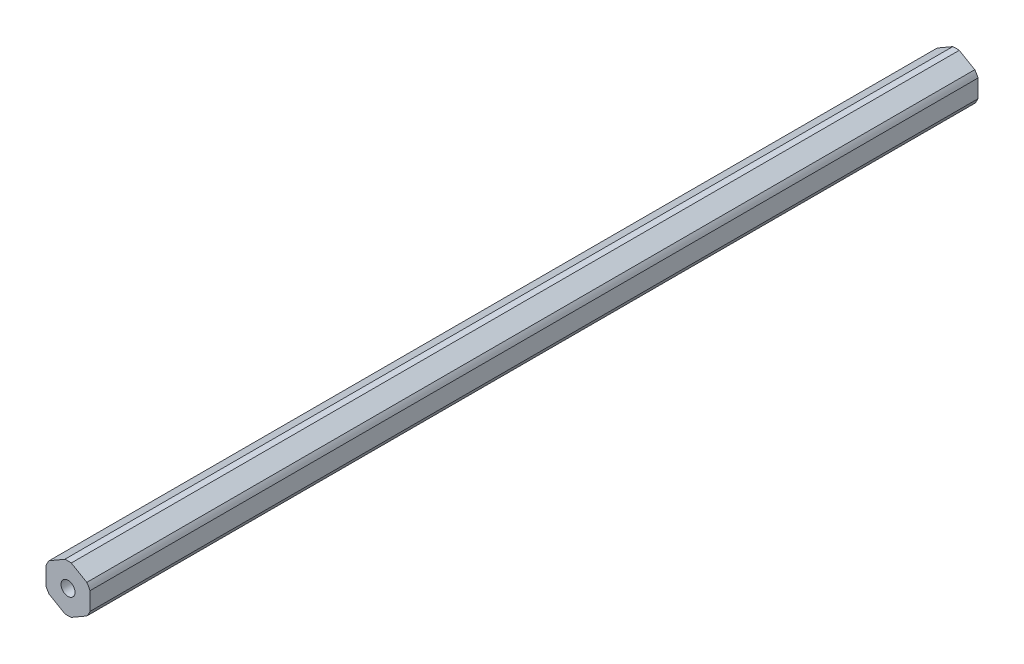
SolidWorks part; units mm, degrees
material "7075-T6 (SN)"
ref_plane "Front Plane" through (0, 0, 0) normal (0, 0, 1) x (1, 0, 0)
ref_plane "Top Plane" through (0, 0, 0) normal (0, 1, 0) x (1, 0, 0)
ref_plane "Right Plane" through (0, 0, 0) normal (1, 0, 0) x (0, 0, -1)
sketch "Sketch1" plane through (0, 0, 0) normal (0, 0, 1) x (1, 0, 0)
  line L1 (0, 7.3323) -> (-6.35, 3.6662)
  line L2 (-6.35, 3.6662) -> (-6.35, -3.6662)
  line L3 (-6.35, -3.6662) -> (0, -7.3323)
  line L4 (0, -7.3323) -> (6.35, -3.6662)
  line L5 (6.35, -3.6662) -> (6.35, 3.6662)
  line L6 (6.35, 3.6662) -> (0, 7.3323)
  circle A0 centre (0, 0) radius 6.35 construction
  circle A1 centre (0, 0) radius 6.858
  dimension "D1" = 12.7
  dimension "D2" = 13.716
extrude "Boss-Extrude1" add sketch "Sketch1" along normal mid plane 256.159 contours L5 A1 L6 L1 L2 L3 L4 region at (0, 0, 0)
sketch "Sketch2" plane through (0, 0, 128.0795) normal (0, 0, 1) x (1, 0, 0)
  circle A0 centre (0, 0) radius 2.0193
  dimension "D1" = 4.0386
extrude "Cut-Extrude1" [suppressed] cut sketch "Sketch2" against normal through all
hole_wizard "#10-32 Tapped Hole1" positions "3DSketch1" profile "Sketch3" tap size "#10-32" standard "ANSI Inch"
sketch3d "3DSketch1"
  line L0 (0, 0, 128.0795) -> (0, 0, -128.0795) construction
  point P0 (0, 0, 128.0795)
  point P4 (0, 0, -128.0795)
sketch "Sketch3" plane through (0, 0, 128.0795) normal (1, 0, 0) x (0, -1, 0)
  line L0 (0, 0) -> (0, 13.1513)
  line L1 (0, 13.1513) -> (2.0193, 11.938)
  line L2 (2.0193, 11.938) -> (2.0193, 0)
  line L5 (2.0193, 0) -> (0, 0)
  line L10 (0, 13.1513) -> (-2.0193, 11.938) construction
  line L11 (0, -6.35) -> (0, 107.95) construction
  dimension "Tap Drill Dia." = 4.0386
  dimension "Tap Drill Depth" = 11.938
  dimension "Drill Angle" = 118
cosmetic thread "Hole Thread1" parameters "D1"=9.652, "D2"=4.826
cosmetic thread "Hole Thread2" parameters "D1"=9.652, "D2"=4.826
